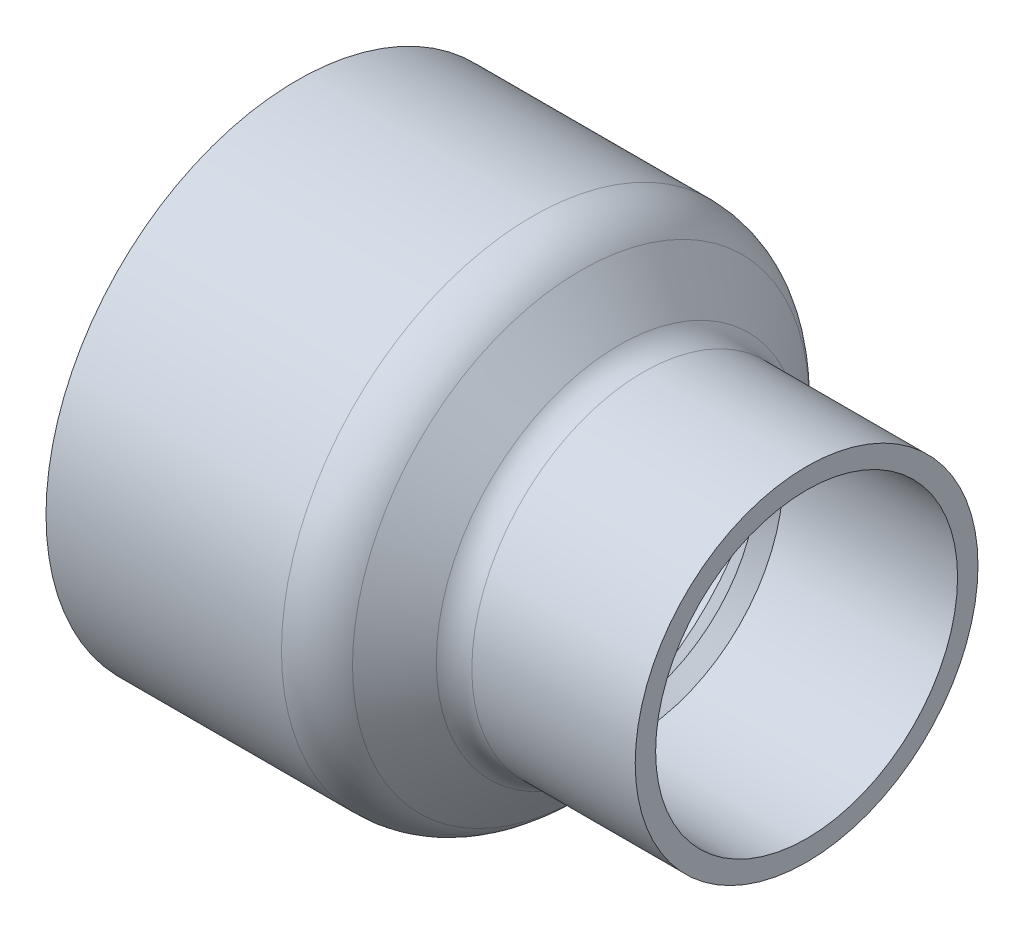
SolidWorks part; units mm, degrees
ref_plane "Front Plane" through (0, 0, 0) normal (0, 0, 1) x (1, 0, 0)
ref_plane "Top Plane" through (0, 0, 0) normal (0, 1, 0) x (1, 0, 0)
ref_plane "Right Plane" through (0, 0, 0) normal (1, 0, 0) x (0, 0, -1)
sketch "Sketch0" plane through (0, 0, 0) normal (0, 0, 1) x (1, 0, 0)
  line L0 (-51.181, 0) -> (16.383, 0) construction
  line L2 (-0.381, 0) -> (16.383, 0) construction
  line L3 (-51.181, 0) -> (51.181, 0) construction
  line L4 (-51.181, 50.3682) -> (-51.181, -50.3682) construction
  line L5 (-0.381, 44.3484) -> (-51.181, 44.6532) construction
  line L6 (-0.381, 44.3484) -> (-0.381, -44.3484) construction
  line L7 (-0.381, -44.3484) -> (-51.181, -44.6532) construction
  line L8 (-51.181, 44.6532) -> (-51.181, -44.6532) construction
  line L9 (51.181, 30.3149) -> (51.181, -30.3149) construction
  line L10 (51.181, 34.417) -> (51.181, -34.417) construction
  line L11 (16.383, 26.2509) -> (16.383, -26.2509) construction
  line L12 (16.383, 30.0863) -> (16.383, -30.0863) construction
  line L13 (16.383, -30.0863) -> (51.181, -30.3149) construction
  line L14 (-0.381, 38.9636) -> (-0.381, -38.9636) construction
  line L15 (16.383, 30.0863) -> (51.181, 30.3149) construction
  dimension "N" = 16.764
  dimension "M" = 100.7364
  dimension "OD A" = 89.3064
  dimension "OD B" = 88.6968
  dimension "ID" = 77.9272
  dimension "L" = 102.362
  dimension "ID2" = 52.5018
  dimension "OD B2" = 60.1726
  dimension "OD A2" = 60.6298
  dimension "M2" = 68.834
  dimension "C" = 50.8
  dimension "C2" = 34.798
sketch "Sketch1" plane through (0, 0, 0) normal (0, 0, 1) x (1, 0, 0)
  line L0 (-51.181, 0) -> (16.383, 0) construction
  line L1 (-51.181, 0) -> (16.383, 0) construction
  line L2 (-0.381, -44.3484) -> (13.5682, -27.7244)
  line L3 (0, -52.7853) -> (-4.3779, -49.1118) construction
  line L4 (-51.181, -50.3682) -> (-51.181, -44.6532)
  line L5 (-51.181, -44.6532) -> (-0.381, -44.3484)
  line L7 (13.5682, -27.7244) -> (16.383, -30.0863)
  line L8 (2.0282, -50.3682) -> (15.4128, -34.417)
  line L9 (2.0282, -50.3682) -> (-51.181, -50.3682)
  line L10 (0, 0) -> (0, -52.7853) construction
  line L12 (16.383, -30.0863) -> (51.181, -30.3149)
  line L13 (51.181, -30.3149) -> (51.181, -34.417)
  line L14 (51.181, -34.417) -> (15.4128, -34.417)
  dimension "D1" = 40
revolve "Revolve1" add sketch "Sketch1" angle 360 about L1
fillet "Fillet1" radius 12.7 1 edges at (2.0282, 0, 50.3682)
fillet "Fillet2" radius 6.35 1 edges at (15.4128, 0, 34.417)
